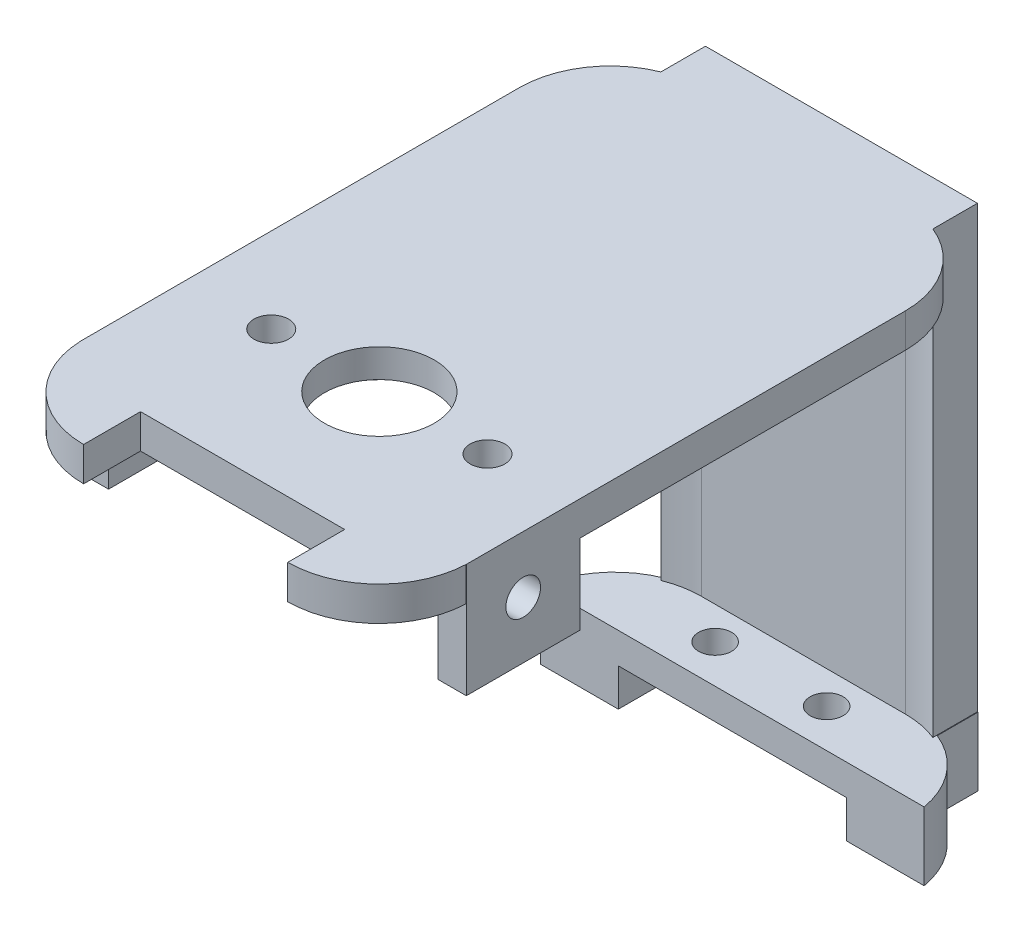
SolidWorks part; units mm, degrees
note: '?' marks a value the reader was unsure of.
ref_plane "Front Plane" through (0, 0, 0) normal (0, 0, 1) x (1, 0, 0)
ref_plane "Top Plane" through (0, 0, 0) normal (0, 1, 0) x (1, 0, 0)
ref_plane "Right Plane" through (0, 0, 0) normal (1, 0, 0) x (0, 0, -1)
sketch "Sketch2" plane through (0, 0, 0) normal (0, 1, 0) x (1, 0, 0)
  line L1 (-53.1096, -52.9171) -> (-53.1242, 1.3691)
  line L5 (-53.1242, 1.3691) -> (-19.1742, 1.3691)
  line L6 (-19.1742, 1.3691) -> (-19.1742, -52.9171)
  line L8 (-53.1096, -52.9171) -> (-19.1742, -52.9171)
  dimension "D1" = 33.95
  dimension "D2" = 54.2862
extrude "Boss-Extrude2" add sketch "Sketch2" along normal blind 3
fillet "Fillet2" radius 8 4 edges at (-19.1742, 1.5, -1.3691) (-53.1242, 1.5, -1.3691) (-53.1096, 1.5, 52.9171) (-19.1742, 1.5, 52.9171)
ref_plane "Plane1" through (0, 0, 25.774) normal (0, 0, 1) x (1, 0, 0)
ref_plane "Plane2" through (-36.1491, 0, 0.0049) normal (-1, 0, 0.0001) x (0.0001, 0, 1)
ref_axis "Axis1" through (-36.1456, 3.15, 25.774) along (0, -1, 0)?
sketch "Sketch3" plane through (0, 3, 0) normal (0, 1, 0) x (1, 0, 0)
  line L0 (-45.1221, 1.3691) -> (-27.1742, 1.3691) construction
  line L1 (-36.1482, 1.3691) -> (-36.1482, 4.7091) construction
  line L2 (-48.0982, 4.7091) -> (-24.1982, 4.7091)
  line L3 (-24.1982, 4.7091) -> (-24.1982, 0.7949)
  line L4 (-45.1221, 1.3691) -> (-27.1742, 1.3691)
  line L5 (-48.0982, 4.7091) -> (-48.0982, 0.7949)
  arc A0 (-19.1742, -6.6309) -> (-27.1742, 1.3691) centre (-27.1742, -6.6309) ccw construction
  arc A1 (-24.1982, 0.7949) -> (-27.1742, 1.3691) centre (-27.1742, -6.6309) ccw
  arc A2 (-48.0982, 0.7949) -> (-45.1221, 1.3691) centre (-45.1221, -6.6309) cw
  dimension "D1" = 3.34
  dimension "D2" = 11.95
extrude "Boss-Extrude3" add sketch "Sketch3" against normal blind 44.7
sketch "Sketch4" plane through (0, -41.7, 0) normal (0, -1, 0) x (1, 0, 0)
  line L0 (-48.1482, -1.1253) -> (-48.1482, -4.7091)
  line L1 (-48.1482, -4.7091) -> (-24.1482, -4.7091)
  line L2 (-24.1482, -4.7091) -> (-24.1482, -1.1253)
  line L3 (-52.9973, 4.8709) -> (-19.299, 4.8709)
  line L4 (-41.0482, 1.4909) -> (-31.2482, 1.4909) construction
  line L5 (-24.1982, -4.7091) -> (-48.0982, -4.7091) construction
  line L6 (-36.1482, -4.7091) -> (-36.1482, -18.3744) construction
  line L7 (-36.1482, -4.7091) -> (-36.1482, -18.3744) construction
  arc A0 (-24.1482, -1.1253) -> (-19.299, 4.8709) centre (-27.1294, 6.2445) ccw
  arc A1 (-52.9973, 4.8709) -> (-48.1482, -1.1253) centre (-45.1669, 6.2445) ccw
  circle A2 centre (-41.0482, 1.4909) radius 1.45
  circle A3 centre (-31.2482, 1.4909) radius 1.45
  dimension "D3" = 2.9
  dimension "D4" = 2.9
  dimension "D9" = 7.95
  dimension "D1" = 9.58
  dimension "D2" = 9.8
  dimension "D5" = 3.38
  dimension "D6" = 3.5838
  dimension "D7" = 7.1
  dimension "D8" = 24
extrude "Boss-Extrude4" add sketch "Sketch4" against normal blind 6
sketch "Sketch5" plane through (0, -41.7, 0) normal (0, -1, 0) x (1, 0, 0)
  line L0 (-31.2482, 1.4909) -> (-41.0482, 1.4909) construction
  line L1 (-26.1232, 4.8709) -> (-26.1232, -2.8389)
  line L3 (-46.1732, 4.8709) -> (-46.1732, -2.8389)
  line L4 (-26.1232, -2.8389) -> (-46.1732, -2.8389)
  line L5 (-46.1732, 1.4909) -> (-41.0482, 1.4909) construction
  line L6 (-31.2482, 1.4909) -> (-26.1232, 1.4909) construction
  line L7 (-19.299, 4.8709) -> (-52.9973, 4.8709) construction
  line L8 (-46.1732, 4.8709) -> (-26.1232, 4.8709)
  circle A0 centre (-31.2482, 1.4909) radius 1.45
  circle A1 centre (-41.0482, 1.4909) radius 1.45
  circle A2 centre (-31.2482, 1.4909) radius 1.45 construction
  point P12 (-31.2482, 1.4909)
  dimension "D2" = 9.8
  dimension "D3" = 20.05
  dimension "D4" = 7.7098
extrude "Cut-Extrude2" cut sketch "Sketch5" against normal blind 3.3
sketch "Sketch7" plane through (-19.1742, 0, 0) normal (1, 0, 0) x (0, 0, -1)
  line L0 (-52.9171, 3) -> (-40.2271, 3) construction
  line L1 (-44.9171, 3) -> (-6.6309, 3) construction
  line L2 (-40.2271, 3) -> (-40.2271, -2) construction
  line L4 (-45.2271, 3) -> (-35.2271, 3)
  line L5 (-45.2271, 3) -> (-45.2271, -7)
  line L6 (-45.2271, -7) -> (-35.2271, -7)
  line L7 (-35.2271, 3) -> (-35.2271, -7)
  circle A0 centre (-40.2271, -2) radius 1.525
  dimension "D3" = 3.05
  dimension "D1" = 12.69
  dimension "D2" = 5
  dimension "D4" = 5
  dimension "D5" = 5
  dimension "D6" = 5
extrude "Boss-Extrude5" add sketch "Sketch7" against normal up to surface (33.9392 mm away)
sketch "Sketch8" plane through (0, -7, 0) normal (0, -1, 0) x (1, 0, 0)
  line L0 (-53.1116, 45.2271) -> (-50.6116, 45.2271) construction
  line L1 (-53.1057, 45.2271) -> (-19.1802, 45.2271) construction
  line L2 (-19.1742, 35.2271) -> (-21.6742, 35.2271) construction
  line L3 (-53.1143, 35.2271) -> (-19.1742, 35.2271) construction
  line L5 (-50.6116, 45.2271) -> (-21.6742, 45.2271)
  line L6 (-50.6116, 45.2271) -> (-50.6116, 35.2271)
  line L7 (-50.6116, 35.2271) -> (-21.6742, 35.2271)
  line L8 (-21.6742, 45.2271) -> (-21.6742, 35.2271)
  dimension "D1" = 2.5
extrude "Cut-Extrude3" cut sketch "Sketch8" against normal up to surface (7 mm away) up to face at (-36.1473, 0, 9.6957)
sketch "Sketch11" plane through (0, 0, 0) normal (0, -1, 0) x (1, 0, 0)
  line L0 (-53.1142, 35.8971) -> (-45.6442, 35.8971) construction
  line L1 (-53.1221, 6.633) -> (-53.1143, 35.2271) construction
  line L2 (-45.6442, 35.8971) -> (-26.6442, 35.8971) construction
  line L3 (-26.6442, 35.8971) -> (-19.1742, 35.8971) construction
  line L4 (-19.1742, 35.2271) -> (-19.1742, 6.6309) construction
  line L5 (-36.143, 52.9171) -> (-36.1442, 35.8971) construction
  line L6 (-45.1117, 52.9171) -> (-27.1742, 52.9171) construction
  circle A0 centre (-45.6442, 35.8971) radius 1.525
  circle A1 centre (-26.6442, 35.8971) radius 1.525
  circle A2 centre (-36.1442, 35.8971) radius 4.825
  dimension "D3" = 3.05
  dimension "D4" = 9.65
  dimension "D1" = 17.02
  dimension "D2" = 19
extrude "Cut-Extrude4" cut sketch "Sketch11" against normal up to surface (3 mm away) up to face at (-36.1456, 3, 24.2232)
sketch "Sketch12" plane through (0, 0, 0) normal (0, -1, 0) x (1, 0, 0)
  circle A0 centre (-36.1442, 35.8971) radius 5.525
  dimension "D1" = 11.05
extrude "Cut-Extrude5" cut sketch "Sketch12" against normal blind 0.5
sketch "Sketch14" plane through (0, 3, 0) normal (0, 1, 0) x (1, 0, 0)
  line L1 (-45.1117, -52.9171) -> (-27.1742, -52.9171)
  line L2 (-45.1117, -52.9171) -> (-45.1117, -47.9171)
  line L3 (-45.1117, -47.9171) -> (-27.1742, -47.9171)
  line L4 (-27.1742, -52.9171) -> (-27.1742, -47.9171)
  point P5 (-27.1742, -52.9171)
  dimension "D2" = 5
extrude "Cut-Extrude6" cut sketch "Sketch14" against normal up to surface (3 mm away) up to face at (-36.1442, 0, 30.3721)
